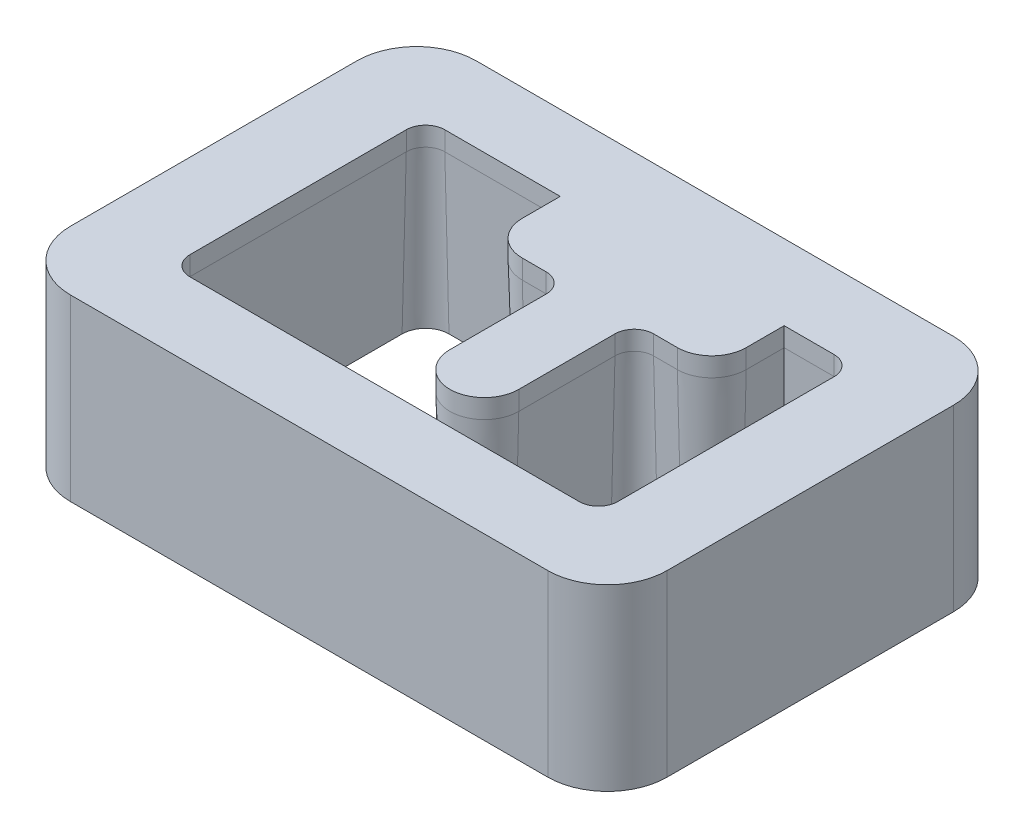
SolidWorks part; units mm, degrees
material "K110"
ref_plane "Front Plane" through (0, 0, 0) normal (0, 0, 1) x (1, 0, 0)
ref_plane "Top Plane" through (0, 0, 0) normal (0, 1, 0) x (1, 0, 0)
ref_plane "Right Plane" through (0, 0, 0) normal (1, 0, 0) x (0, 0, -1)
sketch "Sketch1" plane through (0, 0, 0) normal (0, 1, 0) x (1, 0, 0)
  line L1 (-50, -34) -> (50, -34)
  line L2 (-50, -34) -> (-50, 34)
  line L3 (-50, 34) -> (50, 34)
  line L4 (50, -34) -> (50, 34)
  line L5 (-50, -34) -> (50, 34) construction
  line L6 (-50, 34) -> (50, -34) construction
  point P0 (0, 0)
  dimension "D1" = 68
  dimension "D2" = 100
extrude "Boss-Extrude1" add sketch "Sketch1" against normal blind 30
fillet "Fillet1" radius 10 4 edges at (-50, -15, -34) (50, -15, -34) (50, -15, 34) (-50, -15, 34)
sketch "Sketch2" plane through (0, 0, 0) normal (0, 1, 0) x (1, 0, 0)
  line L22 (-32.625, -21.36) -> (32.625, -21.36)
  line L23 (-35.855, 18.13) -> (-35.855, -18.13)
  line L24 (-13.275, 21.36) -> (-32.625, 21.36)
  line L25 (-13.275, 15) -> (-13.275, 21.36)
  line L26 (-3.505, 9.23) -> (-7.505, 9.23)
  line L27 (-0.275, -10.13) -> (-0.275, 6)
  line L28 (11.265, 6) -> (11.265, -10.13)
  line L29 (18.495, 9.23) -> (14.495, 9.23)
  line L30 (24.265, 21.36) -> (24.265, 15)
  line L31 (32.625, 21.36) -> (24.265, 21.36)
  line L32 (35.855, -18.13) -> (35.855, 18.13)
  line L33 (-32.625, -21.36) -> (32.625, -21.36)
  line L34 (-35.855, 18.13) -> (-35.855, -18.13)
  line L35 (-13.275, 21.36) -> (-32.625, 21.36)
  line L36 (-13.275, 15) -> (-13.275, 21.36)
  line L37 (-3.505, 9.23) -> (-7.505, 9.23)
  line L38 (-0.275, -10.13) -> (-0.275, 6)
  line L39 (11.265, 6) -> (11.265, -10.13)
  line L40 (18.495, 9.23) -> (14.495, 9.23)
  line L41 (24.265, 21.36) -> (24.265, 15)
  line L42 (32.625, 21.36) -> (24.265, 21.36)
  line L43 (35.855, -18.13) -> (35.855, 18.13)
  arc A18 (32.625, -21.36) -> (35.855, -18.13) centre (32.625, -18.13) ccw
  arc A19 (-35.855, -18.13) -> (-32.625, -21.36) centre (-32.625, -18.13) ccw
  arc A20 (-32.625, 21.36) -> (-35.855, 18.13) centre (-32.625, 18.13) ccw
  arc A21 (-13.275, 15) -> (-7.505, 9.23) centre (-7.505, 15) ccw
  arc A22 (-0.275, 6) -> (-3.505, 9.23) centre (-3.505, 6) ccw
  arc A23 (-0.275, -10.13) -> (11.265, -10.13) centre (5.495, -10.13) ccw
  arc A24 (14.495, 9.23) -> (11.265, 6) centre (14.495, 6) ccw
  arc A25 (18.495, 9.23) -> (24.265, 15) centre (18.495, 15) ccw
  arc A26 (35.855, 18.13) -> (32.625, 21.36) centre (32.625, 18.13) ccw
  arc A27 (32.625, -21.36) -> (35.855, -18.13) centre (32.625, -18.13) ccw
  arc A28 (-35.855, -18.13) -> (-32.625, -21.36) centre (-32.625, -18.13) ccw
  arc A29 (-32.625, 21.36) -> (-35.855, 18.13) centre (-32.625, 18.13) ccw
  arc A30 (-13.275, 15) -> (-7.505, 9.23) centre (-7.505, 15) ccw
  arc A31 (-0.275, 6) -> (-3.505, 9.23) centre (-3.505, 6) ccw
  arc A32 (-0.275, -10.13) -> (11.265, -10.13) centre (5.495, -10.13) ccw
  arc A33 (14.495, 9.23) -> (11.265, 6) centre (14.495, 6) ccw
  arc A34 (18.495, 9.23) -> (24.265, 15) centre (18.495, 15) ccw
  arc A35 (35.855, 18.13) -> (32.625, 21.36) centre (32.625, 18.13) ccw
  dimension "D1" = 0.23
extrude "Cut-Extrude1" cut sketch "Sketch2" against normal up to next
sketch "Sketch3" plane through (0, 0, 0) normal (0, 0, 1) x (1, 0, 0)
  line L6 (35.855, -3.2) -> (36.5568, -30)
  line L7 (40, -30) -> (40, 0) construction
  line L8 (40, -30) -> (50, -30) construction
  line L11 (37.4, 0) -> (-37.4, 0) construction
  line L12 (36.5568, -30) -> (34.855, -30)
  line L13 (-40, -30) -> (40, -30) construction
  line L14 (34.855, -3.2) -> (35.855, -3.2)
  line L15 (34.855, -30) -> (34.855, -3.2)
  line L16 (35.855, -30) -> (35.855, 0) construction
  dimension "D1" = 3.2
  dimension "D2" = 1.5
  dimension "D3" = 1
sketch "Sketch5" plane through (0, 0, 0) normal (0, 1, 0) x (1, 0, 0)
  line L0 (32.625, 21.36) -> (24.265, 21.36) construction
  line L1 (35.855, -18.13) -> (35.855, 18.13) construction
  line L2 (24.265, 21.36) -> (24.265, 15) construction
  line L3 (18.495, 9.23) -> (14.495, 9.23) construction
  line L4 (11.265, 6) -> (11.265, -10.13) construction
  line L5 (-0.275, -10.13) -> (-0.275, 6) construction
  line L6 (-3.505, 9.23) -> (-7.505, 9.23) construction
  line L7 (-13.275, 15) -> (-13.275, 21.36) construction
  line L8 (-13.275, 21.36) -> (-32.625, 21.36) construction
  line L9 (-35.855, 18.13) -> (-35.855, -18.13) construction
  line L10 (-32.625, -21.36) -> (32.625, -21.36) construction
  line L11 (-32.625, -21.36) -> (32.625, -21.36)
  line L12 (-35.855, 18.13) -> (-35.855, -18.13)
  line L13 (-13.275, 21.36) -> (-32.625, 21.36)
  line L14 (-13.275, 15) -> (-13.275, 21.36)
  line L15 (-3.505, 9.23) -> (-7.505, 9.23)
  line L16 (-0.275, -10.13) -> (-0.275, 6)
  line L17 (11.265, 6) -> (11.265, -10.13)
  line L18 (18.495, 9.23) -> (14.495, 9.23)
  line L19 (24.265, 21.36) -> (24.265, 15)
  line L20 (35.855, -18.13) -> (35.855, 18.13)
  line L21 (32.625, 21.36) -> (24.265, 21.36)
  arc A0 (-0.275, 6) -> (-3.505, 9.23) centre (-3.505, 6) ccw construction
  arc A1 (35.855, 18.13) -> (32.625, 21.36) centre (32.625, 18.13) ccw construction
  arc A2 (18.495, 9.23) -> (24.265, 15) centre (18.495, 15) ccw construction
  arc A3 (14.495, 9.23) -> (11.265, 6) centre (14.495, 6) ccw construction
  arc A4 (-0.275, -10.13) -> (11.265, -10.13) centre (5.495, -10.13) ccw construction
  arc A5 (-13.275, 15) -> (-7.505, 9.23) centre (-7.505, 15) ccw construction
  arc A6 (-32.625, 21.36) -> (-35.855, 18.13) centre (-32.625, 18.13) ccw construction
  arc A7 (-35.855, -18.13) -> (-32.625, -21.36) centre (-32.625, -18.13) ccw construction
  arc A8 (32.625, -21.36) -> (35.855, -18.13) centre (32.625, -18.13) ccw construction
  arc A9 (32.625, -21.36) -> (35.855, -18.13) centre (32.625, -18.13) ccw
  arc A10 (-35.855, -18.13) -> (-32.625, -21.36) centre (-32.625, -18.13) ccw
  arc A11 (-32.625, 21.36) -> (-35.855, 18.13) centre (-32.625, 18.13) ccw
  arc A12 (-13.275, 15) -> (-7.505, 9.23) centre (-7.505, 15) ccw
  arc A13 (-0.275, 6) -> (-3.505, 9.23) centre (-3.505, 6) ccw
  arc A14 (-0.275, -10.13) -> (11.265, -10.13) centre (5.495, -10.13) ccw
  arc A15 (14.495, 9.23) -> (11.265, 6) centre (14.495, 6) ccw
  arc A16 (18.495, 9.23) -> (24.265, 15) centre (18.495, 15) ccw
  arc A17 (35.855, 18.13) -> (32.625, 21.36) centre (32.625, 18.13) ccw
sweep "Cut-Sweep1" cut profiles "Sketch3" path "Sketch5"
hole_wizard "M6 Tapped Hole1" positions "Sketch11" profile "Sketch9" tap size "M6" standard "ISO"
sketch "Sketch11" plane through (0, -30, 0) normal (0, -1, 0) x (-1, 0, 0)
  line L0 (-40, 34) -> (40, 34) construction
  line L1 (-50, -24) -> (-50, 24) construction
  line L2 (50, 24) -> (50, -24) construction
  line L3 (40, -34) -> (-40, -34) construction
  point P0 (-43, 27)
  point P2 (43, 27)
  point P4 (43, -27)
  point P6 (-43, -27)
  dimension "D1" = 7
  dimension "D2" = 7
  dimension "D3" = 7
  dimension "D4" = 7
sketch "Sketch9" plane through (43, -30, -27) normal (1, 0, 0) x (0, 0, -1)
  line L0 (0, 0) -> (0, 18.5022)
  line L1 (0, 18.5022) -> (2.5, 17)
  line L2 (2.5, 17) -> (2.5, 0.525)
  line L3 (2.5, 0.525) -> (3.025, 0)
  line L5 (3.025, 0) -> (0, 0)
  line L6 (-2.5, 0.525) -> (-3.025, 0) construction
  line L10 (0, 18.5022) -> (-2.5, 17) construction
  line L11 (0, -6.35) -> (0, 107.95) construction
  dimension "Tap Drill Dia." = 5
  dimension "Tap Drill Depth" = 17
  dimension "Near C'Sink Dia." = 6.05
  dimension "Near C'Sink Angle" = 90
  dimension "Drill Angle" = 118
cosmetic thread "Hole Thread1"
cosmetic thread "Hole Thread2"
cosmetic thread "Hole Thread3"
cosmetic thread "Hole Thread4"
